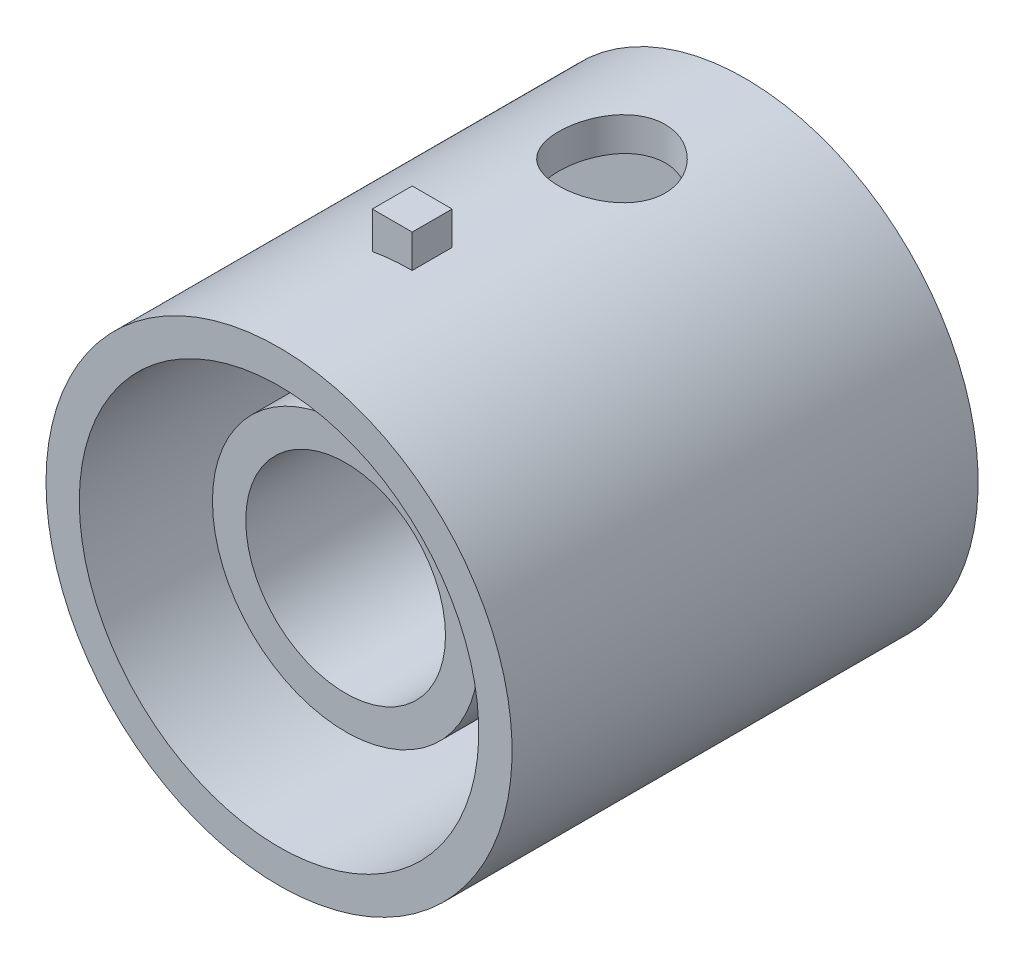
SolidWorks part; units mm, degrees
ref_plane "Front Plane" through (0, 0, 0) normal (0, 0, 1) x (1, 0, 0)
ref_plane "Top Plane" through (0, 0, 0) normal (0, 1, 0) x (1, 0, 0)
ref_plane "Right Plane" through (0, 0, 0) normal (1, 0, 0) x (0, 0, -1)
ref_plane "Plane1" through (0, 0, 0) normal (0, -1, 0) x (1, 0, 0)
sketch "Sketch1" plane through (0, 0, 0) normal (0, -1, 0) x (1, 0, 0)
  line L0 (7.5, 5) -> (0, 5)
  line L1 (0, 5) -> (0, 3)
  line L2 (0, 3) -> (15, 3)
  line L3 (15, 3) -> (15, 0)
  line L4 (15, 0) -> (17.5, 0)
  line L5 (17.5, 0) -> (17.5, 35)
  line L6 (17.5, 35) -> (15, 35)
  line L7 (15, 35) -> (15, 5)
  line L8 (15, 5) -> (10, 5)
  line L9 (10, 5) -> (10, 30)
  line L10 (10, 30) -> (7.5, 30)
  line L11 (7.5, 30) -> (7.5, 5)
  line L12 (0, 35) -> (0, 0) construction
  dimension "D1" = 17.5
revolve "Revolve1" add sketch "Sketch1" angle 360 about L12 reverse direction yes
ref_plane "Plane2" through (0, 0, 25) normal (0, 0, 1) x (1, 0, 0)
sketch "Sketch3" plane through (0, 0, 25) normal (0, 0, 1) x (1, 0, 0)
  line L1 (-3, 15) -> (0, 15)
  line L2 (-3, 15) -> (-3, 20)
  line L3 (-3, 20) -> (0, 20)
  line L4 (0, 15) -> (0, 20)
  line L5 (-3, -20) -> (0, -20)
  line L6 (-3, -20) -> (-3, -15)
  line L7 (-3, -15) -> (0, -15)
  line L8 (0, -20) -> (0, -15)
  dimension "D1" = 3
  dimension "D2" = 5
  dimension "D3" = 3
  dimension "D4" = 5
  dimension "D5" = 15
  dimension "D6" = 15
extrude "Boss-Extrude1" add sketch "Sketch3" against normal blind 3
ref_plane "Plane3" through (0, 13, 0) normal (0, 1, 0) x (1, 0, 0)
ref_axis "Axis1" through (0, 0, 35) along (0, 0, -1)
sketch "Sketch5" plane through (0, 13, 0) normal (0, 1, 0) x (1, 0, 0)
  line L0 (0, -35) -> (0, 0) construction
  line L2 (-7.5, -5) -> (7.5, -5) construction
  circle A0 centre (0, -10) radius 4
  dimension "D1" = 8
  dimension "D2" = 5
extrude "Cut-Extrude1" cut sketch "Sketch5" along normal blind 5
ref_plane "Plane4" through (0, 14.4, 0) normal (0, 1, 0) x (1, 0, 0)
ref_plane "Plane5" through (0, 0, 0) normal (1, 0, 0) x (0, 0, -1)
ref_plane "Plane6" through (0, 0, 10) normal (0, 0, 1) x (1, 0, 0)
ref_axis "Axis2" through (0, 50.3663, 10) along (0, -1, 0)
ref_point "Point1"
ref_plane "Plane7" through (0, 17.5, 0) normal (0, 1, 0) x (1, 0, 0)
ref_point "Point2"
